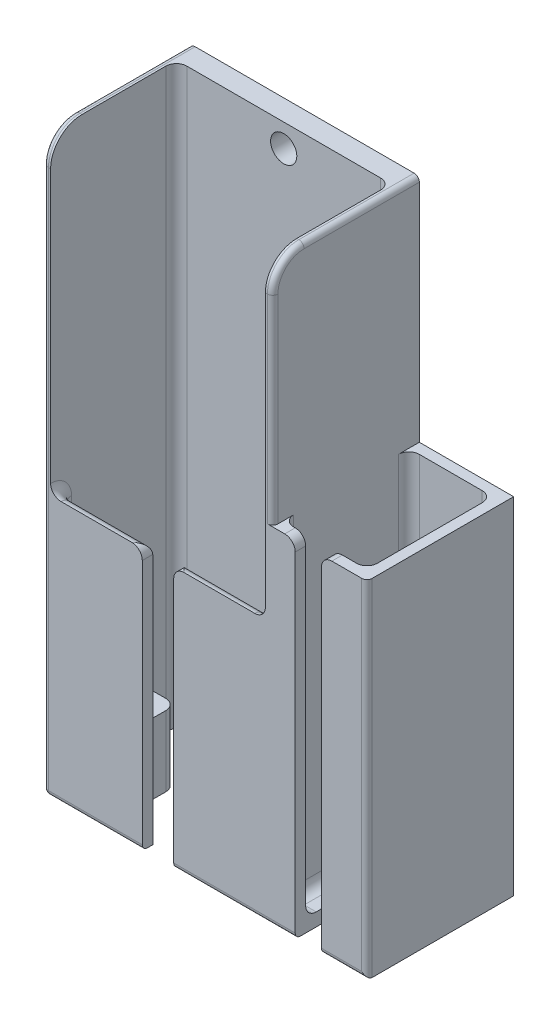
SolidWorks part; units mm, degrees
ref_plane "Front Plane" through (0, 0, 0) normal (0, 0, 1) x (1, 0, 0)
ref_plane "Top Plane" through (0, 0, 0) normal (0, 1, 0) x (1, 0, 0)
ref_plane "Right Plane" through (0, 0, 0) normal (1, 0, 0) x (0, 0, -1)
sketch "Sketch1" plane through (0, 0, 0) normal (0, 0, 1) x (1, 0, 0)
  line L1 (0, 0) -> (55.626, 0)
  line L2 (0, 0) -> (0, -139.7)
  line L3 (0, -139.7) -> (55.626, -139.7)
  line L4 (55.626, 0) -> (55.626, -139.7)
  dimension "D1" = 55.626
  dimension "D2" = 139.7
extrude "Boss-Extrude1" add sketch "Sketch1" along normal blind 35.56
ref_plane "Plane1" through (0, 0, 5.08) normal (0, 0, -1) x (-1, 0, 0)
sketch "Sketch2" plane through (0, 0, 5.08) normal (0, 0, -1) x (-1, 0, 0)
  line L1 (-1.778, -33.02) -> (-53.848, -33.02)
  line L2 (-1.778, -33.02) -> (-1.778, -122.6312)
  line L3 (-1.778, -122.6312) -> (-14.478, -122.6312)
  line L4 (-53.848, -33.02) -> (-53.848, -122.6312)
  line L5 (-1.778, -33.02) -> (-53.848, -122.6312) construction
  line L6 (-1.778, -122.6312) -> (-53.848, -33.02) construction
  line L8 (-55.626, 0) -> (0, 0) construction
  line L10 (0, -139.7) -> (-55.626, -139.7) construction
  line L11 (-14.478, -139.7) -> (-41.148, -139.7)
  line L12 (-14.478, -139.7) -> (-14.478, -122.6312)
  line L14 (-41.148, -139.7) -> (-41.148, -122.6312)
  line L15 (-14.478, -139.7) -> (-41.148, -122.6312) construction
  line L16 (-14.478, -122.6312) -> (-41.148, -139.7) construction
  line L17 (-41.148, -122.6312) -> (-53.848, -122.6312)
  point P0 (-27.813, -77.8256)
  point P13 (-27.813, 0)
  point P14 (-27.813, -131.1656)
  dimension "D1" = 17.0688
  dimension "D2" = 106.68
  dimension "D3" = 52.07
  dimension "D4" = 26.67
extrude "Cut-Extrude1" cut sketch "Sketch2" against normal blind 27.94
sketch "Sketch3" plane through (0, 0, 35.56) normal (0, 0, 1) x (1, 0, 0)
  line L0 (24.003, -139.7) -> (31.623, -139.7)
  line L1 (0, -139.7) -> (55.626, -139.7) construction
  line L2 (31.623, -139.7) -> (31.623, -76.2)
  line L3 (31.623, -76.2) -> (53.848, -76.2)
  line L4 (53.848, 0) -> (1.778, 0)
  line L7 (1.778, 0) -> (1.778, -76.2)
  line L8 (1.778, -76.2) -> (24.003, -76.2)
  line L9 (24.003, -76.2) -> (24.003, -139.7)
  line L11 (53.848, -76.2) -> (53.848, 0)
  line L12 (55.626, 0) -> (0, 0) construction
  line L13 (1.778, -122.6312) -> (1.778, -33.02) construction
  line L14 (53.848, -33.02) -> (53.848, -122.6312) construction
  point P5 (27.813, -139.7)
  point P16 (27.813, -139.7)
  dimension "D1" = 7.62
  dimension "D2" = 63.5
extrude "Cut-Extrude6" cut sketch "Sketch3" against normal blind 30.48
sketch "Sketch4" plane through (0, 0, 0) normal (0, 0, -1) x (-1, 0, 0)
  line L0 (-55.626, 0) -> (0, 0) construction
  line L1 (-53.848, 0) -> (-1.778, 0) construction
  circle A0 centre (-27.813, -5.588) radius 3.175
  point P4 (-27.813, 0)
  dimension "D1" = 6.35
  dimension "D2" = 5.588
extrude "Cut-Extrude7" cut sketch "Sketch4" against normal through all
sketch "Sketch5" plane through (0, -122.6312, 0) normal (0, 1, 0) x (1, 0, 0)
  line L0 (14.478, -33.02) -> (14.478, -5.08) construction
  line L1 (1.778, -5.08) -> (14.478, -5.08)
  line L2 (1.778, -5.08) -> (1.778, -17.78)
  line L3 (1.778, -17.78) -> (14.478, -17.78)
  line L4 (14.478, -5.08) -> (14.478, -17.78)
  line L5 (41.148, -33.02) -> (41.148, -5.08) construction
  line L6 (53.848, -33.02) -> (41.148, -33.02)
  line L7 (53.848, -33.02) -> (53.848, -20.32)
  line L8 (53.848, -20.32) -> (41.148, -20.32)
  line L9 (41.148, -33.02) -> (41.148, -20.32)
  dimension "D1" = 12.7
extrude "Cut-Extrude8" cut sketch "Sketch5" against normal through all
sketch "Sketch6" plane through (0, -139.7, 0) normal (0, -1, 0) x (1, 0, 0)
  line L0 (55.626, 35.56) -> (53.848, 35.56) construction
  line L1 (55.626, 0) -> (78.486, 0)
  line L3 (55.626, 35.56) -> (78.486, 35.56)
  line L4 (78.486, 0) -> (78.486, 35.56)
  line L5 (55.626, 35.56) -> (55.626, 33.02)
  line L6 (55.626, 2.54) -> (75.946, 2.54)
  line L8 (55.626, 33.02) -> (75.946, 33.02)
  line L9 (75.946, 2.54) -> (75.946, 33.02)
  line L10 (55.626, 0) -> (55.626, 2.54)
  line L12 (55.626, 35.56) -> (55.626, 0) construction
  dimension "D1" = 20.32
  dimension "D2" = 2.54
  dimension "D3" = 2.54
  dimension "D4" = 2.54
extrude "Boss-Extrude2" add sketch "Sketch6" against normal blind 83.82
sketch "Sketch7" plane through (0, -139.7, 0) normal (0, -1, 0) x (1, 0, 0)
  line L0 (55.626, 33.02) -> (75.946, 33.02) construction
  line L1 (55.626, 33.02) -> (75.946, 33.02)
  line L2 (55.626, 33.02) -> (55.626, 2.54)
  line L3 (55.626, 2.54) -> (75.946, 2.54)
  line L4 (75.946, 33.02) -> (75.946, 2.54)
  line L5 (55.626, 33.02) -> (55.626, 2.54) construction
  circle A0 centre (64.262, 17.78) radius 6.35
  point P15 (55.626, 17.78)
  dimension "D1" = 12.7
  dimension "D2" = 8.636
extrude "Boss-Extrude3" add sketch "Sketch7" against normal blind 3.175
sketch "Sketch8" plane through (0, 0, 35.56) normal (0, 0, 1) x (1, 0, 0)
  line L0 (78.486, -55.88) -> (55.626, -55.88) construction
  line L1 (61.087, -55.88) -> (67.437, -55.88)
  line L2 (61.087, -55.88) -> (61.087, -139.7)
  line L3 (61.087, -139.7) -> (67.437, -139.7)
  line L4 (67.437, -55.88) -> (67.437, -139.7)
  line L5 (31.623, -139.7) -> (78.486, -139.7) construction
  line L7 (55.626, -55.88) -> (55.626, 0) construction
  point P13 (64.262, -55.88)
  dimension "D1" = 6.35
  dimension "D2" = 8.636
extrude "Cut-Extrude9" cut sketch "Sketch8" against normal blind 17.78
fillet "Fillet1" radius 7.62 6 edges at (14.478, -131.1656, 33.02) (41.148, -131.1656, 5.08) (54.737, 0, 35.56) (0.889, 0, 35.56) (67.437, -138.1125, 23.2793) (61.087, -138.1125, 23.2793)
fillet "Fillet2" radius 2.54 29 edges at (53.848, -131.1656, 20.32) (41.148, -131.1656, 20.32) (55.626, -96.2025, 2.54) (75.946, -96.2025, 2.54) (75.946, -96.2025, 33.02) (55.626, -96.2025, 33.02) (55.626, -136.525, 17.78) (71.6915, -136.525, 33.02) (75.946, -136.525, 17.78) (65.786, -136.525, 2.54) (58.3565, -136.525, 33.02) (61.087, -55.88, 34.29) (67.437, -55.88, 34.29) (1.778, -99.4156, 33.02) (11.938, -122.6312, 33.02) (1.778, -122.6312, 25.4) (43.688, -122.6312, 5.08) (1.778, -69.85, 5.08) (53.848, -61.3156, 5.08) (53.848, -107.95, 33.02) (12.8905, -76.2, 33.02) (1.778, -76.2, 34.29) (42.7355, -76.2, 33.02) (24.003, -76.2, 34.29) (53.848, -76.2, 34.29) (31.623, -76.2, 34.29) (53.848, -122.6312, 12.7) (1.778, -131.1656, 17.78) (14.478, -131.1656, 17.78)
fillet "Fillet3" radius 1.27 10 edges at (55.626, 0, 13.97) (55.626, -2.2318, 33.3282) (0, 0, 13.97) (0, -2.2318, 33.3282) (55.626, -31.75, 35.56) (78.486, -97.79, 35.56) (12.0015, -139.7, 35.56) (46.355, -139.7, 35.56) (0, -139.7, 17.78) (0, -73.66, 35.56)
